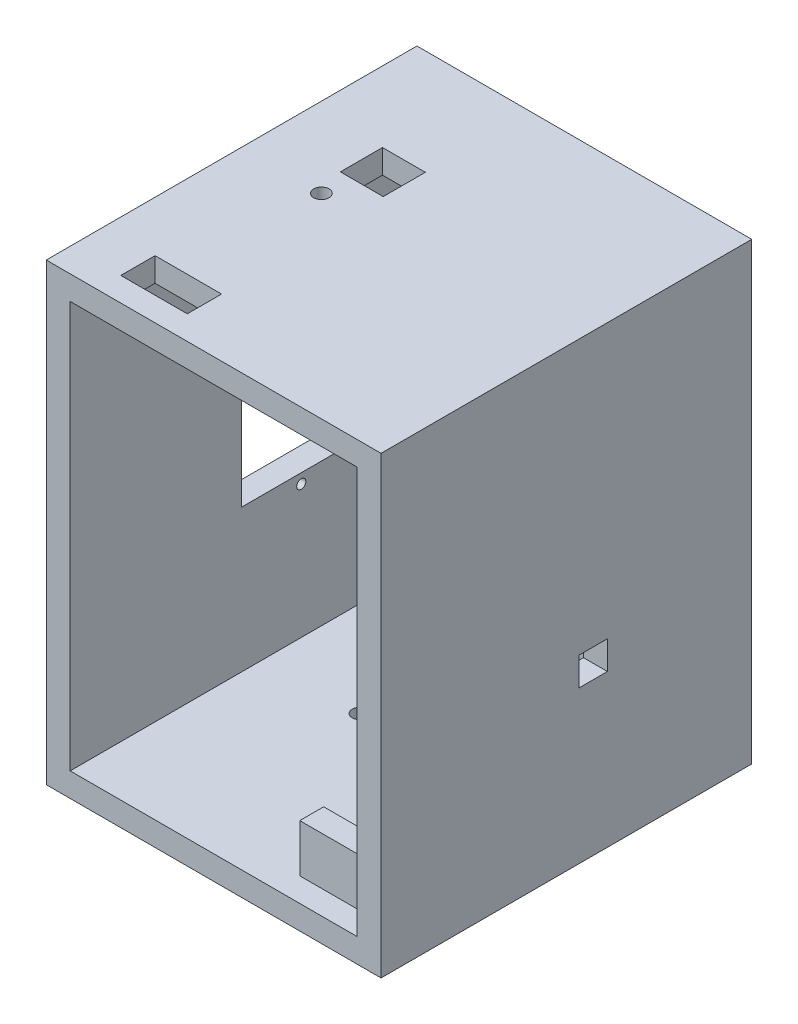
SolidWorks part; units mm, degrees
ref_plane "Front Plane" through (0, 0, 0) normal (0, 0, 1) x (1, 0, 0)
ref_plane "Top Plane" through (0, 0, 0) normal (0, 1, 0) x (1, 0, 0)
ref_plane "Right Plane" through (0, 0, 0) normal (1, 0, 0) x (0, 0, -1)
sketch "Sketch1" plane through (0, 0, 0) normal (0, 0, 1) x (1, 0, 0)
  line L1 (-17.5349, 30.527) -> (52.4651, 30.527)
  line L2 (-17.5349, 30.527) -> (-17.5349, -64.473)
  line L3 (-17.5349, -64.473) -> (52.4651, -64.473)
  line L4 (47.4651, 25.527) -> (-12.5349, 25.527)
  line L5 (-12.5349, 25.527) -> (-12.5349, -59.473)
  line L6 (-12.5349, -59.473) -> (47.4651, -59.473)
  line L7 (47.4651, -59.473) -> (47.4651, 25.527)
  line L8 (47.4651, 25.527) -> (-12.5349, 25.527)
  line L9 (-12.5349, 25.527) -> (-12.5349, -59.473)
  line L10 (-12.5349, -59.473) -> (47.4651, -59.473)
  line L11 (47.4651, -59.473) -> (47.4651, 25.527)
  line L12 (52.4651, 30.527) -> (52.4651, -64.473)
  line L13 (-17.5349, 30.527) -> (52.4651, -64.473) construction
  line L14 (-17.5349, -64.473) -> (52.4651, 30.527) construction
  point P2 (17.4651, -16.973)
  dimension "D2" = 5
  dimension "D3" = 5
  dimension "D4" = 5
  dimension "D5" = 5
  dimension "D1" = 0
extrude "Boss-Extrude1" add sketch "Sketch1" against normal blind 75 contours L12 L1 L2 L3 L11 L10 L9 L8 region at (17.4651, 29.347, 0)
sketch "Sketch2" plane through (-17.5349, 0, 0) normal (-1, 0, 0) x (0, 0, 1)
  line L0 (-59.8109, -17.0822) -> (-59.8109, -28.6392) construction
  line L1 (-60.8109, -29.6392) -> (-35.8239, -29.6392)
  line L2 (-60.8109, -29.6392) -> (-60.8109, -4.5252)
  line L3 (-60.8109, -4.5252) -> (-35.8239, -4.5252)
  line L4 (-35.8239, -29.6392) -> (-35.8239, -4.5252)
  line L5 (-59.8109, -28.6392) -> (-36.8239, -28.6392) construction
  line L6 (-36.8239, -5.5252) -> (-59.8109, -5.5252) construction
  line L7 (-36.8239, -17.0822) -> (-36.8239, -5.5252) construction
  circle A0 centre (-48.3174, -2.4772) radius 0.9525 construction
  circle A1 centre (-48.3174, -31.6872) radius 0.9525 construction
  circle A2 centre (-48.3174, -2.4772) radius 0.9525
  circle A3 centre (-48.3174, -31.6872) radius 0.9525
  dimension "D1" = 1
  dimension "D2" = 1
  dimension "D3" = 1
  dimension "D4" = 1
extrude "Cut-Extrude1" cut sketch "Sketch2" against normal blind 27
sketch "Sketch3" plane through (0, 30.527, 0) normal (0, 1, 0) x (1, 0, 0)
  line L0 (-1.7529, 47.707) -> (5.2067, 47.707) construction
  line L1 (-1.7529, 47.707) -> (5.2067, 47.707)
  line L2 (5.2067, 54.5142) -> (-1.7529, 54.5142) construction
  line L3 (-2.7529, 46.707) -> (6.2067, 46.707)
  line L4 (-2.7529, 46.707) -> (-2.7529, 55.5142)
  line L5 (-2.7529, 55.5142) -> (6.2067, 55.5142)
  line L6 (6.2067, 46.707) -> (6.2067, 55.5142)
  line L7 (-1.7529, 54.5142) -> (-1.7529, 47.707) construction
  line L8 (5.2067, 47.707) -> (5.2067, 54.5142) construction
  line L9 (4.45, 12.1628) -> (-4.45, 12.1628) construction
  line L10 (4.45, 12.1628) -> (-4.45, 12.1628)
  line L11 (47.4651, 0) -> (-12.5349, 0) construction
  line L12 (6.95, 12.1628) -> (-6.95, 12.1628)
  line L13 (6.95, 12.1628) -> (6.95, 5)
  line L14 (6.95, 5) -> (-6.95, 5)
  line L15 (-6.95, 12.1628) -> (-6.95, 5)
  circle A0 centre (-0.8512, 40.8363) radius 1.6129 construction
  circle A1 centre (-0.8512, 40.8363) radius 1.6129
  dimension "D1" = 1
  dimension "D2" = 1
  dimension "D3" = 1
  dimension "D4" = 1
  dimension "D5" = 5
  dimension "D6" = 0
  dimension "D7" = 2.5
  dimension "D8" = 2.5
extrude "Cut-Extrude2" cut sketch "Sketch3" against normal blind 27 contours L3 L6 L5 L4 | A1 | L12 L15 L14 L13 L10 region at (1.7269, 30.527, -51.1106) region at (0, 30.527, -8.5814) region at (-0.8512, 30.527, -40.8363)
sketch "Sketch4" plane through (52.4651, 0, 0) normal (1, 0, 0) x (0, 0, -1)
  line L0 (46.3258, -31.6429) -> (46.3258, -27.7059) construction
  line L1 (47.3258, -32.6429) -> (41.3888, -32.6429)
  line L2 (47.3258, -32.6429) -> (47.3258, -26.7059)
  line L3 (47.3258, -26.7059) -> (41.3888, -26.7059)
  line L4 (41.3888, -32.6429) -> (41.3888, -26.7059)
  line L5 (42.3888, -31.6429) -> (46.3258, -31.6429) construction
  line L6 (46.3258, -27.7059) -> (42.3888, -27.7059) construction
  line L7 (42.3888, -27.7059) -> (42.3888, -31.6429) construction
  dimension "D1" = 1
  dimension "D2" = 1
  dimension "D3" = 1
  dimension "D4" = 1
extrude "Cut-Extrude3" cut sketch "Sketch4" against normal blind 27 contours L3 L4 L1 L2
sketch "Sketch5" plane through (47.4651, 0, 0) normal (-1, 0, 0) x (0, 0, 1)
  line L0 (-38.4772, 5.2125) -> (-38.4772, -47.9243) construction
  line L1 (-5, 25.527) -> (-5, -59.473) construction
  line L2 (-38.4772, 5.2125) -> (-38.4772, -47.9243)
  line L3 (-5, 25.527) -> (-5, -59.473)
  line L5 (-38.4772, -47.9243) -> (-33.4772, -47.9243)
  line L6 (-38.4772, -47.9243) -> (-38.4772, 5.2125)
  line L7 (-38.4772, 5.2125) -> (-33.4772, 5.2125)
  line L8 (-33.4772, -47.9243) -> (-33.4772, 5.2125)
  line L9 (-5, -59.473) -> (-10, -59.473)
  line L10 (-5, -59.473) -> (-5, -49.473)
  line L11 (-5, -49.473) -> (-10, -49.473)
  line L12 (-10, -59.473) -> (-10, -49.473)
  line M8 (-75, -59.473) -> (0, -59.473)
  dimension "D1" = 5
  dimension "D2" = 5
  dimension "D3" = 10
extrude "Boss-Extrude2" add sketch "Sketch5" along normal blind 17 contours L12 L3 L11 M8 | L5 L8 L7 L2 region at (47.4651, -21.3559, -35.9772) region at (47.4651, -54.473, -7.5)
sketch "Sketch6" plane through (0, 0, -38.4772) normal (0, 0, -1) x (-1, 0, 0)
  line L0 (-35.0699, 5.2125) -> (-35.0699, -47.9243) construction
  line L1 (-35.0699, -32.9243) -> (-30.4651, -32.9243)
  line L2 (-35.0699, -32.9243) -> (-35.0699, -9.7875)
  line L3 (-35.0699, -9.7875) -> (-30.4651, -9.7875)
  line L4 (-30.4651, -32.9243) -> (-30.4651, -9.7875)
  line L5 (-30.4651, 5.2125) -> (-30.4651, -47.9243) construction
  line L6 (-30.4651, -47.9243) -> (-47.4651, -47.9243) construction
  line L7 (-30.4651, 5.2125) -> (-47.4651, 5.2125) construction
  dimension "D1" = 15
  dimension "D2" = 15
extrude "Boss-Extrude3" add sketch "Sketch6" along normal blind 17
sketch "Sketch7" plane through (0, 0, -10) normal (0, 0, -1) x (-1, 0, 0)
  circle A0 centre (-43.6551, -55.663) radius 1.27 construction
  circle A1 centre (-43.6551, -55.663) radius 1.27
extrude "Cut-Extrude4" cut sketch "Sketch7" against normal blind 17
sketch "Sketch8" plane through (0, -64.473, 0) normal (0, -1, 0) x (1, 0, 0)
  circle A0 centre (7.3496, -49.5601) radius 5.969 construction
  circle A1 centre (7.3496, -40.6701) radius 1.5875 construction
  circle A2 centre (7.3496, -49.5601) radius 5.969
  circle A3 centre (7.3496, -40.6701) radius 1.5875
  circle A4 centre (7.3496, -49.5601) radius 6.469
  dimension "D1" = 0.5
extrude "Cut-Extrude5" cut sketch "Sketch8" against normal blind 17 contours A2 | A3 region at (7.3496, -64.473, -49.5601) region at (7.3496, -64.473, -40.6701)
sketch "Sketch9" plane through (0, 0, -75) normal (0, 0, -1) x (-1, 0, 0)
  line L4 (-52.4651, 30.527) -> (-52.4651, -64.473)
  line L5 (-52.4651, -64.473) -> (17.5349, -64.473)
  line L6 (17.5349, -64.473) -> (17.5349, 30.527)
  line L7 (17.5349, 30.527) -> (-52.4651, 30.527)
  line L8 (-52.4651, 30.527) -> (-52.4651, -64.473)
  line L9 (-52.4651, -64.473) -> (17.5349, -64.473)
  line L10 (17.5349, -64.473) -> (17.5349, 30.527)
  line L11 (17.5349, 30.527) -> (-52.4651, 30.527)
  dimension "D1" = 0
extrude "Boss-Extrude4" add sketch "Sketch9" along normal mid plane 5
sketch "Sketch10" plane through (0, 0, -77.5) normal (0, 0, -1) x (-1, 0, 0)
  circle A0 centre (-19.6135, 13.0233) radius 4.572 construction
  circle A1 centre (-19.6135, 0.9583) radius 4.572 construction
  circle A2 centre (-19.6135, -11.1067) radius 4.572 construction
  circle A3 centre (-27.3605, -31.6172) radius 1.778 construction
  circle A4 centre (-11.8665, -31.6172) radius 1.778 construction
  circle A5 centre (-19.6135, 13.0233) radius 4.572
  circle A6 centre (-19.6135, 0.9583) radius 4.572
  circle A7 centre (-19.6135, -11.1067) radius 4.572
  circle A8 centre (-27.3605, -31.6172) radius 1.778
  circle A9 centre (-11.8665, -31.6172) radius 1.778
  circle A10 centre (-19.6135, -11.1067) radius 5.572
  circle A11 centre (-19.6135, 0.9583) radius 5.572
  circle A12 centre (-19.6135, 13.0233) radius 5.572
  dimension "D1" = 1
  dimension "D2" = 1
  dimension "D3" = 1
extrude "Cut-Extrude7" cut sketch "Sketch10" against normal blind 24 contours A5 | A12 A5 | A6 | A11 A6 | A9 | A10 | A8 region at (19.6135, 13.0233, -77.5) region at (19.6135, 0.9583, -77.5) region at (11.8665, -31.6172, -77.5) region at (25.0279, 0.9583, -77.5) region at (25.0279, 13.0233, -77.5)
